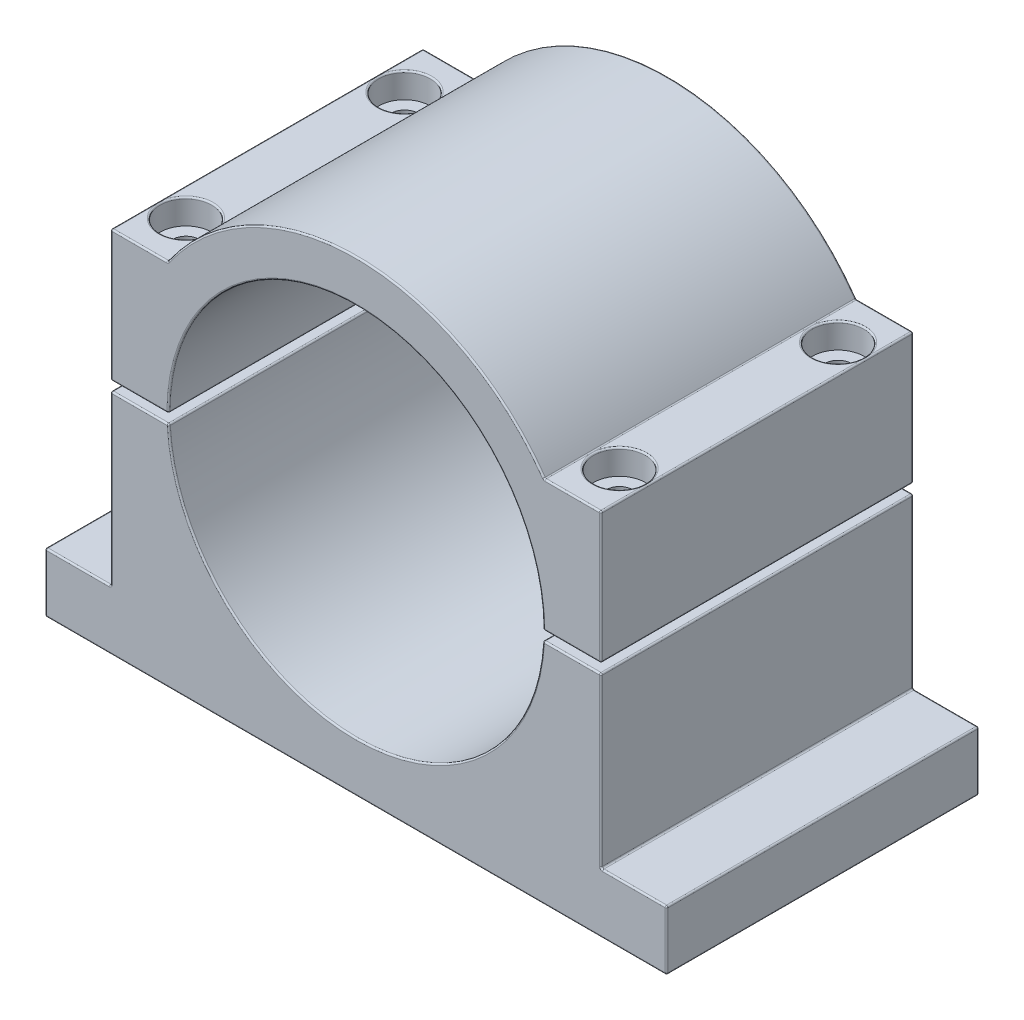
SolidWorks part; units mm, degrees
ref_plane "Спереди" through (0, 0, 0) normal (0, 0, 1) x (1, 0, 0)
ref_plane "Сверху" through (0, 0, 0) normal (0, 1, 0) x (1, 0, 0)
ref_plane "Справа" through (0, 0, 0) normal (1, 0, 0) x (0, 0, -1)
sketch "Эскиз1" plane through (0, 0, 0) normal (0, 0, 1) x (1, 0, 0)
  line L0 (0, 0) -> (0, -76) construction
  line L1 (99.5, -76) -> (-99.5, -76)
  line L2 (-99.5, -76) -> (-99.5, -57)
  line L3 (-99.5, -57) -> (-78.5, -57)
  line L4 (-78.5, -57) -> (-78.5, 42)
  line L5 (-78.5, 42) -> (-60.3179, 42)
  line L6 (0, 73.5) -> (0, 60) construction
  line L7 (0, -76) -> (0, -60) construction
  line L8 (-78.5, -1.5) -> (0, -1.5) construction
  line L9 (0, 0) -> (78.5, 0)
  line L10 (78.5, -3) -> (-78.5, -3)
  line L11 (0, -3) -> (0, 0)
  line L12 (0, 0) -> (-78.5, 0)
  line L13 (-78.5, -3) -> (-78.5, 0)
  line L14 (78.5, 42) -> (60.3179, 42)
  line L15 (78.5, -57) -> (78.5, 42)
  line L16 (99.5, -57) -> (78.5, -57)
  line L17 (99.5, -76) -> (99.5, -57)
  circle A0 centre (0, 0) radius 60
  circle A1 centre (0, 0) radius 73.5
  point P20 (-60, 0)
  dimension "D1" = 120
  dimension "D2" = 149.5
  dimension "D3" = 199
  dimension "D4" = 19
  dimension "D5" = 21
  dimension "D6" = 16
  dimension "D7" = 99
  dimension "D8" = 3
  dimension "D9" = 43.5
extrude "Бобышка-Вытянуть1" add sketch "Эскиз1" along normal mid plane 100 contours A1 L10 L4 L3 L2 L1 L17 L16 L15 | L10 A1 A0 | L9 A1 L12 A0 | A1 L5 L4 L12 | A1 L9 L15 L14 region at (0, -73.8803, 0) region at (0, -71.8708, 0) region at (73.0762, 25.8984, 0) region at (-73.0762, 25.8984, 0) region at (66.75, 1.6435, 0)
sketch "Эскиз2" plane through (0, 42, 0) normal (0, 1, 0) x (1, 0, 0)
  line L0 (-78.5, 50) -> (-60.3179, 50) construction
  line L1 (-69.409, 50) -> (-69.409, -50) construction
  line L2 (-78.5, -50) -> (-60.3179, -50) construction
  line L4 (69.409, -35) -> (-69.409, -35) construction
  line L5 (69.409, -35) -> (69.409, 35) construction
  line L6 (69.409, 35) -> (-69.409, 35) construction
  line L7 (-69.409, -35) -> (-69.409, 35) construction
  line L8 (69.409, -35) -> (-69.409, 35) construction
  line L9 (69.409, 35) -> (-69.409, -35) construction
  circle A0 centre (-69.409, 35) radius 8.25
  circle A1 centre (-69.409, -35) radius 8.25
  circle A2 centre (69.409, -35) radius 8.25
  circle A3 centre (69.409, 35) radius 8.25
  point P6 (0, 0)
  dimension "D2" = 16.5
  dimension "D3" = 16.5
  dimension "D4" = 16.5
  dimension "D5" = 16.5
  dimension "D1" = 70
extrude "Вырез-Вытянуть1" cut sketch "Эскиз2" against normal blind 8
sketch "Эскиз3" plane through (0, 34, 0) normal (0, 1, 0) x (1, 0, 0)
  circle A0 centre (-69.409, 35) radius 4.25
  circle A1 centre (69.409, 35) radius 4.25
  circle A2 centre (69.409, -35) radius 4.25
  circle A3 centre (-69.409, -35) radius 4.25
  dimension "D1" = 8.5
extrude "Вырез-Вытянуть2" cut sketch "Эскиз3" against normal through all
sketch "Эскиз4" plane through (0, -3, 0) normal (0, 1, 0) x (1, 0, 0)
  circle A0 centre (-69.409, 35) radius 3.1
  circle A1 centre (-69.409, -35) radius 3.1
  circle A2 centre (69.409, -35) radius 3.1
  circle A3 centre (69.409, 35) radius 3.1
  dimension "D1" = 6.2
extrude "Вырез-Вытянуть3" cut sketch "Эскиз4" against normal blind 30
fillet "Скругление1" radius 0.5 28 edges at (-60, 0, 0) (60, 0, 0) (78.5, 0, 0) (78.5, 42, 0) (61.159, 42, -35) (61.159, 42, 35) (-77.659, 42, -35) (-77.659, 42, 35) (78.5, 21, -50) (69.409, 42, -50) (-69.409, 42, -50) (-69.25, 0, -50) (0, 60, -50) (69.25, 0, -50) (-78.5, 42, 0) (-78.5, 0, 0) (-78.5, 21, -50) (60.3179, 42, 0) (-60.3179, 42, 0) (0, 73.5, -50) (0, 60, 50) (-69.25, 0, 50) (-78.5, 21, 50) (-69.409, 42, 50) (0, 73.5, 50) (69.409, 42, 50) (78.5, 21, 50) (69.25, 0, 50)
fillet "Скругление2" radius 0.5 30 edges at (99.5, -57, 0) (78.5, -57, 0) (78.5, -3, 0) (-99.5, -57, 0) (-78.5, -3, 0) (-78.5, -57, 0) (-99.5, -76, 0) (99.5, -76, 0) (78.5, -30, 50) (89, -57, 50) (99.5, -66.5, 50) (0, -76, 50) (-99.5, -66.5, 50) (-89, -57, 50) (-78.5, -30, 50) (-69.2125, -3, 50) (69.2125, -3, 50) (-69.2125, -3, -50) (-78.5, -30, -50) (-89, -57, -50) (-99.5, -66.5, -50) (0, -76, -50) (99.5, -66.5, -50) (89, -57, -50) (78.5, -30, -50) (69.2125, -3, -50) (59.925, -3, 0) (0, -60, 50) (-59.925, -3, 0) (0, -60, -50)
